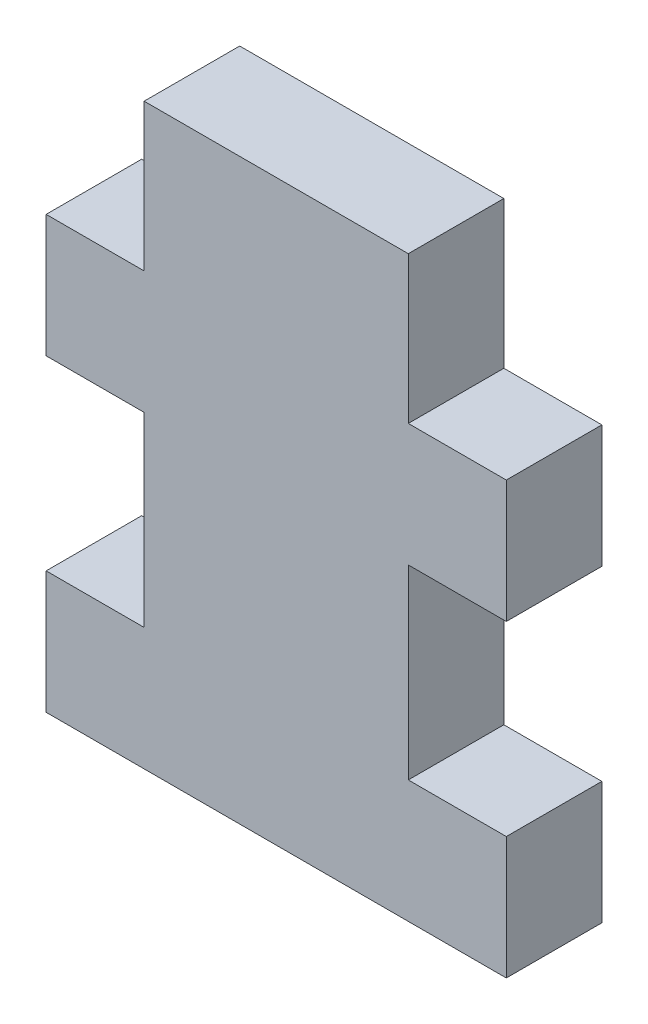
SolidWorks part; units mm, degrees
ref_plane "Front" through (0, 0, 0) normal (0, 0, 1) x (1, 0, 0)
ref_plane "Top" through (0, 0, 0) normal (0, 1, 0) x (1, 0, 0)
ref_plane "Right" through (0, 0, 0) normal (1, 0, 0) x (0, 0, -1)
ref_axis "side-side" through (80.9, 0, 0) along (-1, 0, 0)
ref_axis "up-down" through (0, 50, 0) along (0, -1, 0)
ref_axis "front-back" through (0, 0, -80.9) along (0, 0, 1)
sketch "Sketch1" plane through (0, 0, 0) normal (0, 0, 1) x (1, 0, 0)
  line L0 (6.8453, 49.403) -> (6.8453, 69.723) construction
  line L1 (6.8453, 60.833) -> (6.8453, 70.485)
  line L2 (-6.8453, 49.403) -> (-6.8453, 69.723) construction
  line L3 (-6.8453, 60.833) -> (-6.8453, 70.485)
  line L4 (6.8453, 54.483) -> (-6.8453, 54.483) construction
  line L5 (11.9253, 54.483) -> (-11.9253, 54.483)
  line L6 (6.8453, 84.455) -> (-6.8453, 84.455)
  line L7 (11.9253, 60.833) -> (6.8453, 60.833)
  line L8 (11.9253, 60.833) -> (11.9253, 54.483)
  line L9 (11.9253, 76.835) -> (6.8453, 76.835)
  line L10 (-11.9253, 60.833) -> (-11.9253, 54.483)
  line L11 (11.9253, 76.835) -> (11.9253, 70.485)
  line L12 (11.9253, 70.485) -> (6.8453, 70.485)
  line L13 (-11.9253, 76.835) -> (-11.9253, 70.485)
  line L14 (6.8453, 76.835) -> (6.8453, 84.455)
  line L15 (-6.8453, 76.835) -> (-6.8453, 84.455)
  line L16 (-6.8453, 70.485) -> (-11.9253, 70.485)
  line L17 (-6.8453, 60.833) -> (-11.9253, 60.833)
  line L18 (-6.8453, 76.835) -> (-11.9253, 76.835)
  dimension "D1" = 5.08
  dimension "D2" = 5.08
  dimension "D3" = 6.35
  dimension "D4" = 7.62
  dimension "D5" = 6.35
extrude "Boss-Extrude1" add sketch "Sketch1" along normal mid plane 4.953
